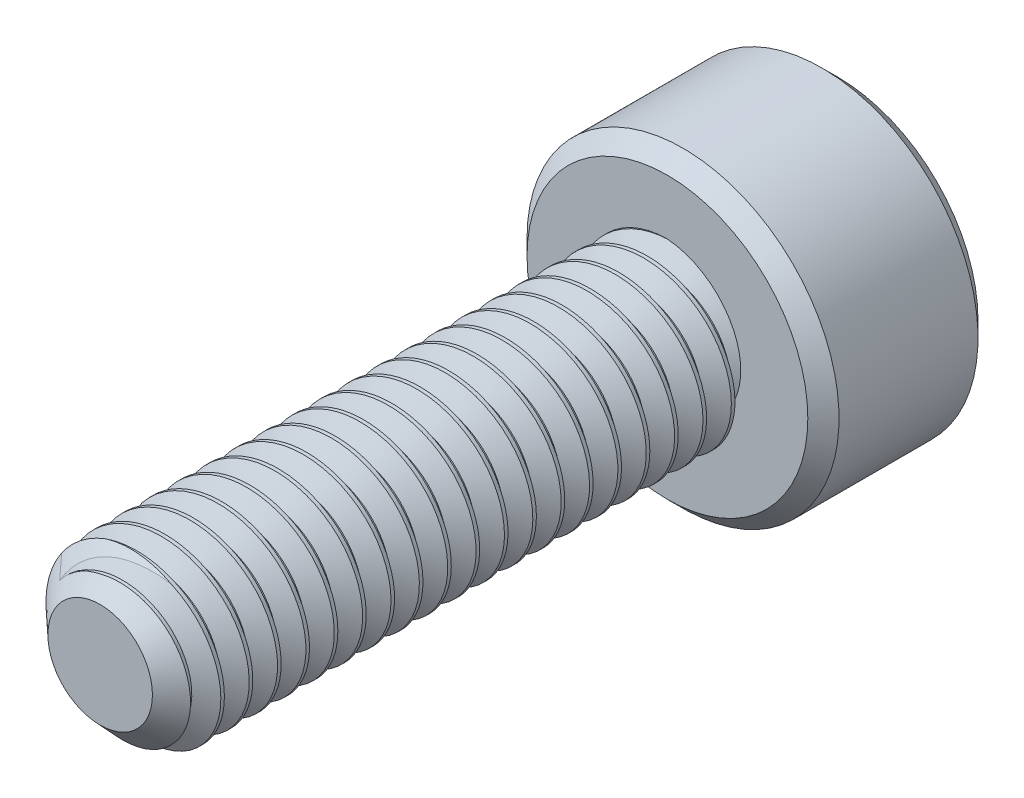
SolidWorks part; units mm, degrees
ref_plane "Front Plane" through (0, 0, 0) normal (0, 0, 1) x (1, 0, 0)
ref_plane "Top Plane" through (0, 0, 0) normal (0, 1, 0) x (1, 0, 0)
ref_plane "Right Plane" through (0, 0, 0) normal (1, 0, 0) x (0, 0, -1)
sketch "Sketch1" plane through (0, 0, 0) normal (0, 0, 1) x (1, 0, 0)
  circle A0 centre (0, 0) radius 1.5
  dimension "OD" = 3
extrude "Extrude1" add sketch "Sketch1" against normal blind 10
sketch "Sketch2" plane through (0, 0, 0) normal (0, 0, 1) x (1, 0, 0)
  circle A0 centre (0, 0) radius 1.5 construction
  circle A1 centre (0, 0) radius 1.5
curve "Helix/Spiral1" pitch 0.5 height 10.5 radius 1.5 centre (0, 0, 0) axis (0, 0, -1) start towards (0, 1, 0) parameters "pitch"=0.5
sketch "Sketch3" plane through (0, 0, 0) normal (1, 0, 0) x (0, 0, -1)
  line L0 (-0.4375, 1.5) -> (-0.25, 1.1752)
  line L1 (-0.25, 1.1752) -> (-0.1875, 1.1752)
  line L2 (-0.1875, 1.1752) -> (0, 1.5)
  line L3 (-0.4375, 1.5) -> (0, 1.5)
  line L4 (-0.2187, 1.5) -> (-0.2187, 1.1752) construction
  line L5 (-0.3438, 1.3376) -> (-0.0937, 1.3376) construction
  line L6 (0, 1.5) -> (0, -1.5) construction
  dimension "D1" = 0.0625
  dimension "D2" = 0.25
  dimension "D3" = 60
sweep "Cut-Sweep1" cut profiles "Sketch3" path "Helix/Spiral1"
sketch "Sketch4" plane through (0, 0, 0) normal (1, 0, 0) x (0, 0, -1)
  line L0 (0.5397, 1.5) -> (0, 0.9212)
  line L1 (0, 0.9212) -> (0, 1.5)
  line L2 (0.5397, 1.5) -> (0, 1.5)
  line L3 (-0.4375, 1.5) -> (0, 1.5) construction
  line L4 (0, 0) -> (7.0209, 0) construction
  dimension "D1" = 47
  dimension "D2" = 0.254
revolve "Cut-Revolve1" cut sketch "Sketch4" angle 360 about L4
sketch "Sketch5" plane through (0, 0, 0) normal (1, 0, 0) x (0, 0, -1)
  line L0 (10, -1.1822) -> (10, 1.0703) construction
  line L1 (10, 1.627) -> (28.1202, 1.627)
  line L2 (10, 1.627) -> (10, 0)
  line L3 (10, 0) -> (28, 0)
  line L4 (28, 1.2968) -> (28, 0)
  line L5 (28.1202, 1.627) -> (28, 1.2968)
  line L6 (0, 0) -> (9.9695, 0) construction
  point P3 (28, 1.627)
  point P10 (28, 1.627)
  dimension "D1" = 0.3302
  dimension "Thread min" = 28
  dimension "D2" = 0.127
  dimension "D3" = 20
revolve "partially thread" [suppressed] add sketch "Sketch5" angle 360 about L6
sketch "Sketch6" plane through (0, 0, -10) normal (0, 0, -1) x (-1, 0, 0)
  circle A0 centre (0, 0) radius 2.75
  dimension "head dia" = 5.5
extrude "Extrude2" add sketch "Sketch6" along normal blind 3
sketch "Sketch7" plane through (0, 0, -13) normal (0, 0, -1) x (-1, 0, 0)
  line L1 (0, 1.4434) -> (-1.25, 0.7217)
  line L2 (-1.25, 0.7217) -> (-1.25, -0.7217)
  line L3 (-1.25, -0.7217) -> (0, -1.4434)
  line L4 (0, -1.4434) -> (1.25, -0.7217)
  line L5 (1.25, -0.7217) -> (1.25, 0.7217)
  line L6 (1.25, 0.7217) -> (0, 1.4434)
  circle A0 centre (0, 0) radius 1.25 construction
  dimension "hex dia" = 2.5
extrude "Cut-Extrude1" cut sketch "Sketch7" against normal blind 1.875
sketch "Sketch8" plane through (0, 0, -13) normal (0, 0, -1) x (-1, 0, 0)
  circle A0 centre (0, 0) radius 1.4434
extrude "Cut-Extrude2" cut sketch "Sketch8" against normal through all draft 45
chamfer "Chamfer1" distance 0.275 angle 45 2 edges at (-2.75, 0, -13) (-2.75, 0, -10)
sketch "Sketch9" plane through (0, 0, 0) normal (1, 0, 0) x (0, 0, -1)
  line L0 (0, 1.5) -> (0, -1.5) construction
  line L1 (2.75, 1.5) -> (2.75, -1.5) construction
  dimension "D1" = 2.75
equation "\"D3@Helix/Spiral1\" = \"screw length@Extrude1\"+\"pitch@Helix/Spiral1\""
equation "\"D1@Sketch3\" = \"pitch@Helix/Spiral1\"*.125"
equation "\"D2@Sketch3\" = \"pitch@Helix/Spiral1\"*.5"
equation "\"D1@Cut-Extrude1\" = \"hex dia@Sketch7\"*.75"
equation "\"D1@Chamfer1\" = \"head dia@Sketch6\"*.05"
equation "\"D1@Sketch9\" = \"pitch@Helix/Spiral1\"*5.5"
